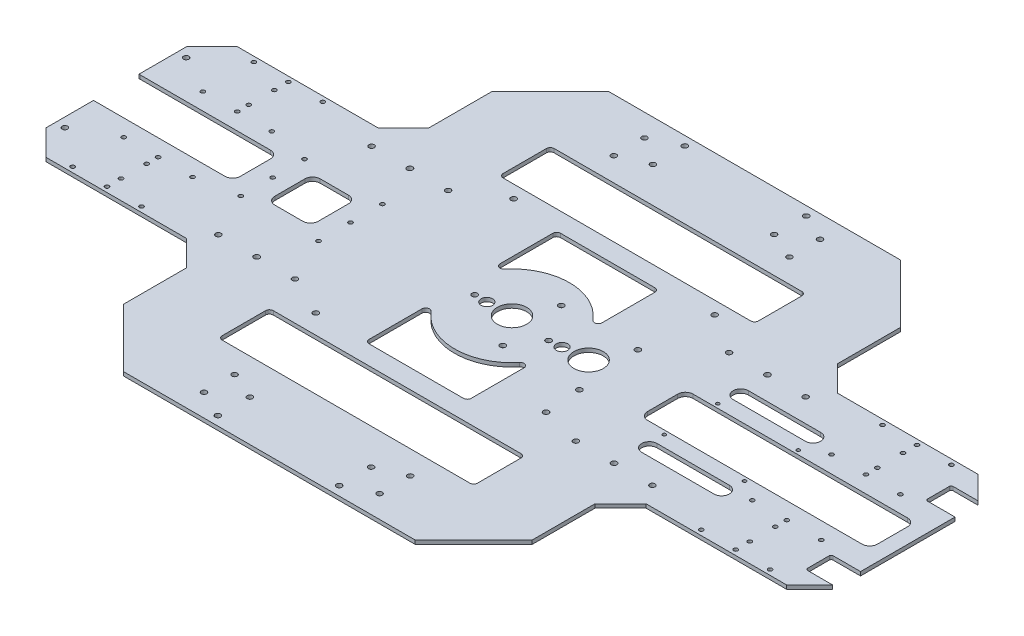
SolidWorks part; units mm, degrees
material "6061 合金"
ref_plane "前视基准面" through (0, 0, 0) normal (0, 0, 1) x (1, 0, 0)
ref_plane "上视基准面" through (0, 0, 0) normal (0, 1, 0) x (1, 0, 0)
ref_plane "右视基准面" through (0, 0, 0) normal (1, 0, 0) x (0, 0, -1)
sketch "草图1" plane through (0, 0, 0) normal (0, 1, 0) x (1, 0, 0)
  line L0 (-310, 75) -> (310, -75) construction
  line L1 (-260, 200) -> (260, 200) construction
  line L2 (-260, 200) -> (-260, -200) construction
  line L3 (-260, -200) -> (260, -200) construction
  line L4 (260, 200) -> (260, -200) construction
  line L5 (310, 75) -> (-310, -75) construction
  line L6 (-160, 200) -> (160, -200) construction
  line L7 (-310, -75) -> (-160, -75)
  line L8 (-310, -75) -> (-310, 75)
  line L9 (-310, 75) -> (-160, 75)
  line L10 (310, -75) -> (310, 75)
  line L11 (160, 200) -> (-160, -200) construction
  line L13 (-160, -200) -> (160, -200)
  line L14 (-160, -200) -> (-160, -75)
  line L15 (-160, 200) -> (160, 200)
  line L16 (160, -200) -> (160, -75)
  line L19 (-160, 75) -> (-160, 200)
  line L22 (160, 75) -> (310, 75)
  line L25 (160, 75) -> (160, 200)
  line L28 (160, -75) -> (310, -75)
  point P0 (0, 0)
  point P6 (-0.5159, 0.1248)
  point P11 (0, 0)
  dimension "D1" = 520
  dimension "D2" = 400
  dimension "D3" = 50
  dimension "D4" = 125
  dimension "D5" = 100
extrude "凸台-拉伸1" add sketch "草图1" along normal blind 3
chamfer "倒角1" distance 20 angle 45 8 edges at (-160, 1.5, -75) (-310, 1.5, -75) (-310, 1.5, 75) (-160, 1.5, 75) (160, 1.5, 75) (160, 1.5, -75) (310, 1.5, 75) (310, 1.5, -75)
sketch "草图2" plane through (0, 3, 0) normal (0, 1, 0) x (1, 0, 0)
  line L0 (-160, 200) -> (-160, 95) construction
  line L1 (-160, 180) -> (160, 180)
  line L2 (-160, 180) -> (-160, 200)
  line L3 (-160, 200) -> (160, 200)
  line L4 (160, 180) -> (160, 200)
  line L6 (160, -200) -> (-160, -200)
  line L7 (160, -200) -> (160, -180)
  line L8 (160, -180) -> (-160, -180)
  line L9 (-160, -200) -> (-160, -180)
  dimension "D1" = 20
  dimension "D2" = 20
extrude "切除-拉伸1" cut sketch "草图2" against normal blind 5
chamfer "倒角2" distance 50 angle 45 4 edges at (-160, 1.5, -180) (-160, 1.5, 180) (160, 1.5, -180) (160, 1.5, 180)
sketch "草图3" plane through (0, 3, 0) normal (0, 1, 0) x (1, 0, 0)
  line L0 (0, 0) -> (144.0598, 0) construction
  line L1 (110, -180) -> (-110, -180) construction
  circle A0 centre (-327.7002, 47.5) radius 2.1
  circle A1 centre (-302.7002, 47.5) radius 2.1
  circle A2 centre (-47.5, 182.8263) radius 2.1
  circle A3 centre (-47.5, 157.8263) radius 2.1
  circle A4 centre (47.5, 182.8263) radius 2.1
  circle A5 centre (47.5, 157.8263) radius 2.1
  circle A6 centre (302.7002, 47.5) radius 2.1
  circle A7 centre (327.7002, 47.5) radius 2.1
  circle A8 centre (-68.75, 172.5) radius 2.1
  circle A9 centre (-68.75, 148.5) radius 2.1
  circle A10 centre (68.75, 172.5) radius 2.1
  circle A11 centre (68.75, 148.5) radius 2.1
  circle A12 centre (68.75, -148.5) radius 2.1
  circle A13 centre (68.75, -172.5) radius 2.1
  circle A14 centre (-68.75, -148.5) radius 2.1
  circle A15 centre (-68.75, -172.5) radius 2.1
  circle A16 centre (327.7002, -47.5) radius 2.1
  circle A17 centre (302.7002, -47.5) radius 2.1
  circle A18 centre (47.5, -157.8263) radius 2.1
  circle A19 centre (47.5, -182.8263) radius 2.1
  circle A20 centre (-47.5, -157.8263) radius 2.1
  circle A21 centre (-47.5, -182.8263) radius 2.1
  circle A22 centre (-302.7002, -47.5) radius 2.1
  circle A23 centre (-327.7002, -47.5) radius 2.1
  dimension "D1" = 4.2
  dimension "D2" = 4.2
  dimension "D3" = 4.2
  dimension "D4" = 4.2
  dimension "D5" = 4.2
  dimension "D6" = 4.2
  dimension "D7" = 4.2
  dimension "D8" = 4.2
  dimension "D9" = 180
extrude "切除-拉伸2" cut sketch "草图3" against normal blind 80
sketch "草图4" plane through (0, 0, 0) normal (0, -1, 0) x (1, 0, 0)
  circle A0 centre (-78.74, 74.91) radius 2.15
  arc A1 (-76.765, 74.91) -> (-80.715, 74.91) centre (-78.74, 74.91) ccw construction
  circle A2 centre (-78.74, -80.01) radius 2.15
  circle A3 centre (78.74, -80.01) radius 2.15
  circle A4 centre (78.74, 52.07) radius 2.15
  dimension "D1" = 4.3
  dimension "D2" = 4.3
  dimension "D3" = 4.3
  dimension "D4" = 4.3
extrude "切除-拉伸3" cut sketch "草图4" against normal blind 10
sketch "草图5" plane through (0, 3, 0) normal (0, 1, 0) x (1, 0, 0)
  line L0 (0, 0) -> (90.3311, 0) construction
  line L1 (0, 0) -> (0, 46.0052) construction
  circle A0 centre (219.2002, 71) radius 1.6
  circle A1 centre (273.2002, 71) radius 1.6
  circle A2 centre (246.2002, 71) radius 1.6
  circle A3 centre (219.2002, 30.9984) radius 1.6
  circle A4 centre (246.2002, 30.9984) radius 1.6
  circle A5 centre (273.2002, 30.9984) radius 1.6
  circle A6 centre (246.2002, 60) radius 1.6
  circle A7 centre (246.2002, 40) radius 1.6
  circle A8 centre (246.2002, -40) radius 1.6
  circle A9 centre (246.2002, -60) radius 1.6
  circle A10 centre (273.2002, -30.9984) radius 1.6
  circle A11 centre (246.2002, -30.9984) radius 1.6
  circle A12 centre (219.2002, -30.9984) radius 1.6
  circle A13 centre (246.2002, -71) radius 1.6
  circle A14 centre (273.2002, -71) radius 1.6
  circle A15 centre (219.2002, -71) radius 1.6
  circle A16 centre (-219.2002, -71) radius 1.6
  circle A17 centre (-273.2002, -71) radius 1.6
  circle A18 centre (-246.2002, -71) radius 1.6
  circle A19 centre (-219.2002, -30.9984) radius 1.6
  circle A20 centre (-246.2002, -30.9984) radius 1.6
  circle A21 centre (-273.2002, -30.9984) radius 1.6
  circle A22 centre (-246.2002, -60) radius 1.6
  circle A23 centre (-246.2002, -40) radius 1.6
  circle A24 centre (-246.2002, 40) radius 1.6
  circle A25 centre (-246.2002, 60) radius 1.6
  circle A26 centre (-273.2002, 30.9984) radius 1.6
  circle A27 centre (-246.2002, 30.9984) radius 1.6
  circle A28 centre (-219.2002, 30.9984) radius 1.6
  circle A29 centre (-246.2002, 71) radius 1.6
  circle A30 centre (-273.2002, 71) radius 1.6
  circle A31 centre (-219.2002, 71) radius 1.6
  circle A32 centre (170, -60) radius 2.1
  circle A34 centre (110, -60) radius 2.1
  circle A35 centre (140, -60) radius 2.2
  circle A36 centre (140, 60) radius 2.2
  circle A37 centre (110, 60) radius 2.1
  circle A38 centre (170, 60) radius 2.1
  circle A39 centre (-170, 60) radius 2.1
  circle A40 centre (-110, 60) radius 2.1
  circle A41 centre (-140, 60) radius 2.2
  circle A42 centre (-140, -60) radius 2.2
  circle A43 centre (-110, -60) radius 2.1
  circle A44 centre (-170, -60) radius 2.1
  dimension "D1" = 3.2
extrude "切除-拉伸4" cut sketch "草图5" against normal blind 29
sketch "草图6" plane through (0, 3, 0) normal (0, 1, 0) x (1, 0, 0)
  line L0 (160, -150) -> (160, -95) construction
  line L1 (0, 0) -> (166.252, 0) construction
  line L2 (-160, 130) -> (-110, 180)
  line L3 (110, 180) -> (-110, 180)
  line L4 (110, 180) -> (160, 130)
  line L5 (-160, -95) -> (-160, -150) construction
  line L12 (160, -144.1421) -> (160, -130)
  line L13 (114.1421, -190) -> (160, -144.1421)
  line L14 (52.4797, -190) -> (114.1421, -190)
  line L15 (-114.1421, -190) -> (-52, -190)
  line L16 (-160, -144.1421) -> (-114.1421, -190)
  line L17 (-160, -130) -> (-160, -144.1421)
  line L25 (-52, -190) -> (52.4797, -190)
  line L28 (110, -180) -> (160, -130) construction
  line L29 (110, -180) -> (-110, -180) construction
  line L30 (-160, -130) -> (-110, -180) construction
  line L31 (110, -180) -> (160, -130)
  line L32 (110, -180) -> (-110, -180)
  line L33 (-160, -130) -> (-110, -180)
  line L37 (-52, 190) -> (52.4797, 190)
  line L38 (-160, 130) -> (-160, 144.1421)
  line L39 (-160, 144.1421) -> (-114.1421, 190)
  line L40 (-114.1421, 190) -> (-52, 190)
  line L41 (52.4797, 190) -> (114.1421, 190)
  line L42 (114.1421, 190) -> (160, 144.1421)
  line L43 (160, 144.1421) -> (160, 130)
  dimension "D1" = 10
  dimension "D2" = 10
  dimension "D3" = 10
extrude "凸台-拉伸2" add sketch "草图6" against normal blind 3 contours L2 | L33 L17 L16 L15 L25 L14 L13 L12 L31 L32 region at (-156.7442, 3, -137.0711) region at (134.7689, 3, 164.7689)
sketch "草图7" plane through (0, 3, 0) normal (0, 1, 0) x (1, 0, 0)
  line L0 (310, -55) -> (310, 55) construction
  line L1 (310, 37) -> (287, 37)
  line L2 (310, 37) -> (310, 57)
  line L3 (310, 57) -> (287, 57)
  line L4 (287, 37) -> (287, 57)
  line L5 (290, 75) -> (180, 75) construction
  line L6 (310, -37) -> (287, -37)
  line L7 (310, -37) -> (310, -57)
  line L8 (310, -57) -> (287, -57)
  line L9 (287, -37) -> (287, -57)
  line L10 (180, -75) -> (290, -75) construction
  dimension "D1" = 18
  dimension "D2" = 20
  dimension "D3" = 20
  dimension "D4" = 18
  dimension "D5" = 23
extrude "切除-拉伸5" cut sketch "草图7" against normal blind 3
fillet "圆角1" radius 1.5 4 edges at (287, 1.5, 37) (287, 1.5, 57) (287, 1.5, -37) (287, 1.5, -57)
sketch "草图9" plane through (0, 0, 0) normal (0, -1, 0) x (1, 0, 0)
  line L0 (-45.449, 182.8784) -> (-49.551, 182.8784) construction
  line L1 (49.551, 182.8784) -> (45.449, 182.8784) construction
  line L2 (0, 0) -> (154.6544, 0) construction
  circle A0 centre (-47.5, 182.8784) radius 2.15
  circle A1 centre (47.5, 182.8784) radius 2.15
  circle A2 centre (47.5, -182.8784) radius 2.15
  circle A3 centre (-47.5, -182.8784) radius 2.15
  dimension "D1" = 4.3
extrude "切除-拉伸6" cut sketch "草图9" against normal blind 3
sketch "草图10" plane through (0, 0, 0) normal (0, -1, 0) x (1, 0, 0)
  circle A0 centre (60, 0) radius 11.5
  circle A1 centre (40.8185, 1.6223) radius 4.5
  circle A2 centre (72.3318, -26.2474) radius 2.15
  circle A3 centre (76.565, 23.8034) radius 2.15
  circle A4 centre (31.1032, 2.4441) radius 2.15
  dimension "D1" = 4.3
  dimension "D2" = 23
  dimension "D3" = 9
extrude "切除-拉伸7" cut sketch "草图10" against normal blind 5
sketch "草图11" plane through (0, 0, 0) normal (0, -1, 0) x (1, 0, 0)
  line L0 (-290, 75) -> (-180, 75) construction
  line L2 (-187.4745, 25) -> (-126.5, 25) construction
  line L3 (-187.4745, 25) -> (-187.4745, -25) construction
  line L4 (-187.4745, -25) -> (-126.5, -25) construction
  line L5 (-126.5, 25) -> (-126.5, -25) construction
  line L6 (-187.4745, 25) -> (-126.5, 25) construction
  line L7 (-187.4745, 25) -> (-187.4745, 0) construction
  line L8 (-187.4745, 0) -> (-126.5, 0) construction
  line L9 (-126.5, 25) -> (-126.5, 0) construction
  circle A6 centre (-126.5, -25) radius 1.6
  circle A7 centre (-187.5, -25) radius 1.6
  circle A8 centre (-126.5, 0) radius 1.6
  circle A9 centre (-187.4745, 0) radius 1.6
  circle A10 centre (-187.4745, 25) radius 1.6
  circle A11 centre (-126.5, 25) radius 1.6
  dimension "D1" = 50
  dimension "D2" = 25
  dimension "D3" = 60.9745
extrude "切除-拉伸8" cut sketch "草图11" against normal blind 10
sketch "草图12" plane through (0, 0, 0) normal (0, -1, 0) x (1, 0, 0)
  circle A0 centre (60, 0) radius 140
  dimension "D1" = 280
sketch "草图13" plane through (0, 3, 0) normal (0, 1, 0) x (1, 0, 0)
  line L0 (143.4002, 35.8) -> (200.0002, 35.8) construction
  line L1 (143.4002, 41.8) -> (200.0002, 41.8)
  line L2 (143.4002, 29.8) -> (200.0002, 29.8)
  line L3 (143.4002, -35.8) -> (200.0002, -35.8) construction
  line L4 (143.4002, -29.8) -> (200.0002, -29.8)
  line L5 (143.4002, -41.8) -> (200.0002, -41.8)
  line L6 (137.4002, 15.5) -> (137.4002, 21) construction
  line L7 (206.0002, -21) -> (206.0002, 21) construction
  line L8 (137.4002, -21) -> (137.4002, -15.5) construction
  line L9 (140.2002, 23.8) -> (203.2002, 23.8) construction
  line L10 (140.2002, -23.8) -> (203.2002, -23.8) construction
  circle A0 centre (140.2002, 21) radius 1.35
  circle A1 centre (203.2002, 21) radius 1.35
  circle A2 centre (203.2002, -21) radius 1.35
  circle A3 centre (140.2002, -21) radius 1.35
  arc A4 (143.4002, 41.8) -> (143.4002, 29.8) centre (143.4002, 35.8) ccw
  arc A5 (200.0002, 29.8) -> (200.0002, 41.8) centre (200.0002, 35.8) ccw
  arc A6 (143.4002, -29.8) -> (143.4002, -41.8) centre (143.4002, -35.8) ccw
  arc A7 (200.0002, -41.8) -> (200.0002, -29.8) centre (200.0002, -35.8) ccw
  point P14 (171.7002, 35.8)
  point P19 (171.7002, -35.8)
  dimension "D3" = 6
  dimension "D6" = 6
  dimension "D1" = 6
  dimension "D2" = 6
  dimension "D4" = 6
  dimension "D5" = 6
  dimension "D7" = 6
  dimension "D8" = 6
extrude "切除-拉伸9" cut sketch "草图13" against normal blind 3
sketch "草图14" plane through (0, 3, 0) normal (0, 1, 0) x (1, 0, 0)
  line L0 (143.4002, 29.8) -> (200.0002, 29.8) construction
  line L1 (292, 17.8) -> (124, 17.8)
  line L2 (298, 11.8) -> (298, -11.8)
  line L3 (292, -17.8) -> (124, -17.8)
  line L4 (118, 11.8) -> (118, -11.8)
  line L5 (200.0002, -29.8) -> (143.4002, -29.8) construction
  line L6 (310, -37) -> (310, 37) construction
  arc A0 (292, 17.8) -> (298, 11.8) centre (292, 11.8) cw
  arc A1 (298, -11.8) -> (292, -17.8) centre (292, -11.8) cw
  arc A2 (124, -17.8) -> (118, -11.8) centre (124, -11.8) cw
  arc A3 (124, 17.8) -> (118, 11.8) centre (124, 11.8) ccw
  point P12 (298, 17.8)
  point P19 (118, 17.8)
  dimension "D5" = 6
  dimension "D1" = 12
  dimension "D2" = 12
  dimension "D3" = 12
  dimension "D4" = 180
extrude "切除-拉伸10" cut sketch "草图14" against normal blind 3
sketch "草图15" plane through (0, 3, 0) normal (0, 1, 0) x (1, 0, 0)
  line L0 (60, 0) -> (-109.9354, 0) construction
  line L1 (72.3318, 26.2474) -> (-47.4576, 26.2474) construction
  line L2 (76.565, -23.8034) -> (-55.7658, -23.8034) construction
  line L3 (40.8185, -1.6223) -> (-96.5262, 0.8923) construction
  circle A0 centre (76.565, -23.8034) radius 2.15 construction
  circle A1 centre (72.3318, 26.2474) radius 2.15 construction
  circle A2 centre (31.1032, -2.4441) radius 2.15 construction
  circle A3 centre (40.8185, -1.6223) radius 4.5 construction
  circle A4 centre (60, 0) radius 11.5 construction
  circle A5 centre (76.565, -23.8034) radius 2.15
  circle A6 centre (72.3318, 26.2474) radius 2.15
  circle A7 centre (31.1032, -2.4441) radius 2.15
  circle A8 centre (40.8185, -1.6223) radius 4.5
  circle A9 centre (60, 0) radius 11.5
  circle A10 centre (16.565, -23.8034) radius 2.15
  circle A11 centre (12.3318, 26.2474) radius 2.15
  circle A12 centre (-28.8968, -0.3459) radius 2.15
  circle A13 centre (-19.1815, -0.5238) radius 4.5
  circle A14 centre (0, 0) radius 11.5
  dimension "D1" = 60
  dimension "D2" = 60
  dimension "D3" = 60
  dimension "D4" = 60
  dimension "D5" = 60
extrude "切除-拉伸11" cut sketch "草图15" against normal blind 3
sketch "草图16" plane through (0, 3, 0) normal (0, 1, 0) x (1, 0, 0)
  line L2 (-114.1421, 190) -> (114.1421, 190) construction
  line L7 (-97, 130) -> (97, 130)
  line L8 (-100, 127) -> (-100, 93)
  line L44 (-97, 90) -> (-40, 90)
  line L45 (-40, -90) -> (40, -90)
  line L53 (100, 127) -> (100, 93)
  line L70 (-40, 130) -> (40, 130)
  line L71 (-40, 72) -> (-40, 30.5778)
  line L72 (-40, -130) -> (40, -130)
  line L73 (40, 72) -> (40, 30.5778)
  line L74 (-97, -90) -> (-40, -90)
  line L75 (-100, -93) -> (-100, -127)
  line L76 (-97, -130) -> (97, -130)
  line L77 (100, -93) -> (100, -127)
  line L78 (-114.1421, -190) -> (114.1421, -190) construction
  line L79 (160, 95) -> (160, 144.1421) construction
  line L80 (-160, 144.1421) -> (-160, 95) construction
  line L81 (40, 90) -> (97, 90)
  line L82 (-40, -30.5778) -> (-40, -72)
  line L83 (40, -30.5778) -> (40, -72)
  line L84 (40, -90) -> (97, -90)
  line L85 (-37, -75) -> (37, -75)
  line L87 (-40, 90) -> (40, 90)
  line L89 (-37, 75) -> (37, 75)
  arc A56 (-34.6875, -28.6667) -> (34.6875, -28.6667) centre (0, 0) ccw
  arc A57 (34.6875, 28.6667) -> (-34.6875, 28.6667) centre (0, 0) ccw
  arc A58 (-40, -72) -> (-37, -75) centre (-37, -72) ccw
  arc A59 (37, -75) -> (40, -72) centre (37, -72) ccw
  arc A60 (97, -130) -> (100, -127) centre (97, -127) ccw
  arc A61 (97, -90) -> (100, -93) centre (97, -93) cw
  arc A62 (-100, -127) -> (-97, -130) centre (-97, -127) ccw
  arc A63 (-97, -90) -> (-100, -93) centre (-97, -93) ccw
  arc A64 (-100, 93) -> (-97, 90) centre (-97, 93) ccw
  arc A65 (-97, 130) -> (-100, 127) centre (-97, 127) ccw
  arc A66 (97, 130) -> (100, 127) centre (97, 127) cw
  arc A67 (97, 90) -> (100, 93) centre (97, 93) ccw
  arc A68 (37, 75) -> (40, 72) centre (37, 72) cw
  arc A69 (-40, 72) -> (-37, 75) centre (-37, 72) cw
  arc A70 (-34.6875, -28.6667) -> (-40, -30.5778) centre (-37, -30.5778) ccw
  arc A71 (40, -30.5778) -> (34.6875, -28.6667) centre (37, -30.5778) ccw
  arc A72 (40, 30.5778) -> (34.6875, 28.6667) centre (37, 30.5778) cw
  arc A73 (-34.6875, 28.6667) -> (-40, 30.5778) centre (-37, 30.5778) cw
  point P39 (100, -130)
  point P42 (100, -90)
  point P53 (100, 130)
  point P56 (100, 90)
  point P63 (-40, -20.6155)
  point P68 (40, 20.6155)
  dimension "D5" = 60
  dimension "D11" = 90
  dimension "D14" = 3
  dimension "D1" = 60
  dimension "D2" = 60
  dimension "D3" = 60
  dimension "D4" = 60
  dimension "D6" = 60
  dimension "D7" = 60
  dimension "D8" = 60
  dimension "D9" = 40
  dimension "D10" = 40
  dimension "D12" = 15
  dimension "D13" = 15
extrude "切除-拉伸12" cut sketch "草图16" against normal blind 3 contours L81 A67 L53 A66 L7 A65 L8 A64 L44 L87 | A73 A57 A72 L73 A68 L89 A69 L71 | L83 A71 A56 A70 L82 A58 L85 A59 | L74 A63 L75 A62 L76 L72 A60 L77 A61 L84 L45 region at (0, 3, -110) region at (0, 3, 110) region at (0, 3, -56.2095) region at (0, 3, 56.2095)
sketch "草图17" plane through (0, 3, 0) normal (0, 1, 0) x (1, 0, 0)
  line L1 (-308.8279, 17.8) -> (-207, 17.8)
  line L2 (-314.8279, 11.8) -> (-314.8279, -11.8)
  line L3 (-308.8279, -17.8) -> (-207, -17.8)
  line L4 (-201, 11.8) -> (-201, -11.8)
  line L5 (-168, 17.8) -> (-146, 17.8)
  line L6 (-174, 11.8) -> (-174, -11.8)
  line L7 (-168, -17.8) -> (-146, -17.8)
  line L8 (-140, 11.8) -> (-140, -11.8)
  line L14 (-326.8279, 33.3431) -> (-326.8279, -33.3431) construction
  arc A4 (-146, 17.8) -> (-140, 11.8) centre (-146, 11.8) cw
  arc A5 (-146, -17.8) -> (-140, -11.8) centre (-146, -11.8) ccw
  arc A6 (-174, -11.8) -> (-168, -17.8) centre (-168, -11.8) ccw
  arc A7 (-168, 17.8) -> (-174, 11.8) centre (-168, 11.8) ccw
  arc A8 (-207, 17.8) -> (-201, 11.8) centre (-207, 11.8) cw
  arc A9 (-207, -17.8) -> (-201, -11.8) centre (-207, -11.8) ccw
  arc A10 (-314.8279, -11.8) -> (-308.8279, -17.8) centre (-308.8279, -11.8) ccw
  arc A11 (-308.8279, 17.8) -> (-314.8279, 11.8) centre (-308.8279, 11.8) ccw
  dimension "D1" = 12
extrude "切除-拉伸13" cut sketch "草图17" against normal blind 3
